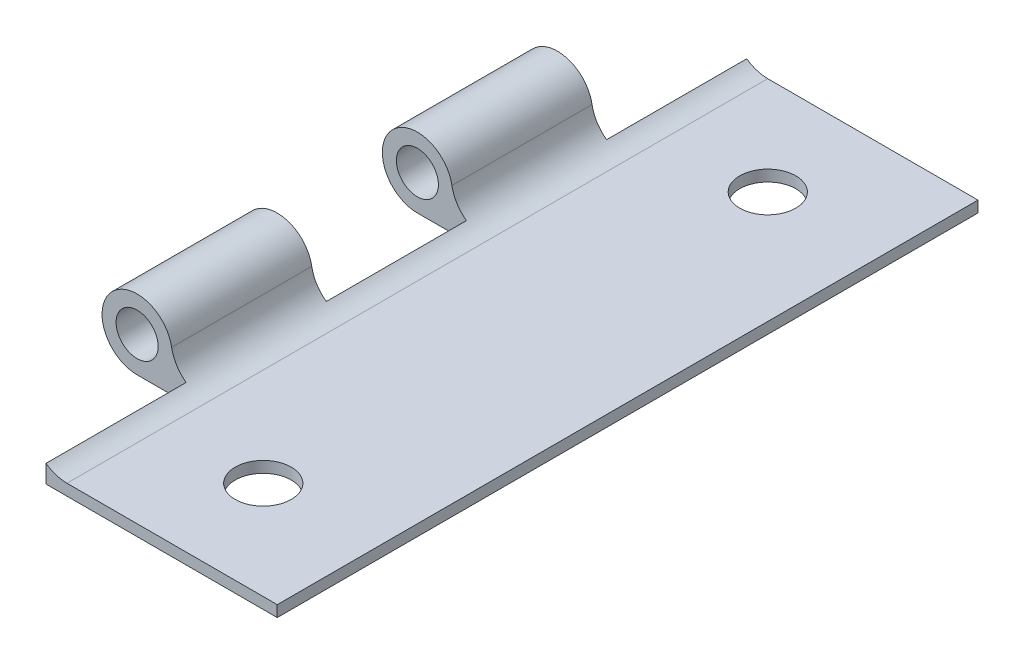
SolidWorks part; units mm, degrees
material "Aço cromo inoxidável"
ref_plane "Plano frontal" through (0, 0, 0) normal (0, 0, 1) x (1, 0, 0)
ref_plane "Plano superior" through (0, 0, 0) normal (0, 1, 0) x (1, 0, 0)
ref_plane "Plano direito" through (0, 0, 0) normal (1, 0, 0) x (0, 0, -1)
sketch "Esboço1" plane through (0, 0, 0) normal (0, 0, 1) x (1, 0, 0)
  line L0 (0, 0) -> (-20, 0)
  line L2 (-15, 0.8) -> (0, 0.8)
  line L3 (0, 0.8) -> (0, 0)
  arc A0 (-20, 0) -> (-18.2893, 4.323) centre (-20, 2.5) cw
  arc A1 (-18.2893, 4.323) -> (-17.5375, 2.9315) centre (-20, 2.5) cw
  arc A2 (-17.5375, 2.9315) -> (-15, 0.8) centre (-15, 3.3762) ccw
  circle A3 centre (-20, 2.5) radius 1.5
  dimension "D4" = 20
  dimension "D5" = 1
  dimension "D2" = 3
  dimension "D1" = 0.8
  dimension "D3" = 5
extrude "Ressalto-extrusão1" add sketch "Esboço1" along normal blind 50
sketch "Esboço2" plane through (0, 0, 0) normal (0, -1, 0) x (1, 0, 0)
  line L0 (-22.5, 50) -> (-22.5, 0) construction
  line L1 (-22.5, 0) -> (-16.5, 0)
  line L2 (-22.5, 0) -> (-22.5, 10)
  line L3 (-22.5, 10) -> (-16.5, 10)
  line L4 (-16.5, 0) -> (-16.5, 10)
  line L5 (0, 50) -> (0, 0) construction
  line L6 (-22.5, 0) -> (-17.5375, 0) construction
  line L7 (-22.5, 20) -> (-22.5, 30)
  line L8 (-22.5, 20) -> (-16.5, 20)
  line L9 (-16.5, 20) -> (-16.5, 30)
  line L10 (-22.5, 30) -> (-16.5, 30)
  line L11 (-22.5, 40) -> (-22.5, 50)
  line L12 (-22.5, 40) -> (-16.5, 40)
  line L13 (-16.5, 40) -> (-16.5, 50)
  line L14 (-22.5, 50) -> (-16.5, 50)
  line L15 (0, 25) -> (-9.0945, 25) construction
  line L16 (0, 50) -> (-15, 50) construction
  circle A0 centre (-8, 43) radius 2
  circle A1 centre (-8, 7) radius 2
  dimension "D5" = 4
  dimension "D1" = 10
  dimension "D2" = 3
  dimension "D3" = 10
  dimension "D4" = 6
  dimension "D6" = 8
  dimension "D7" = 7
extrude "Corte-extrusão2" cut sketch "Esboço2" against normal through all
